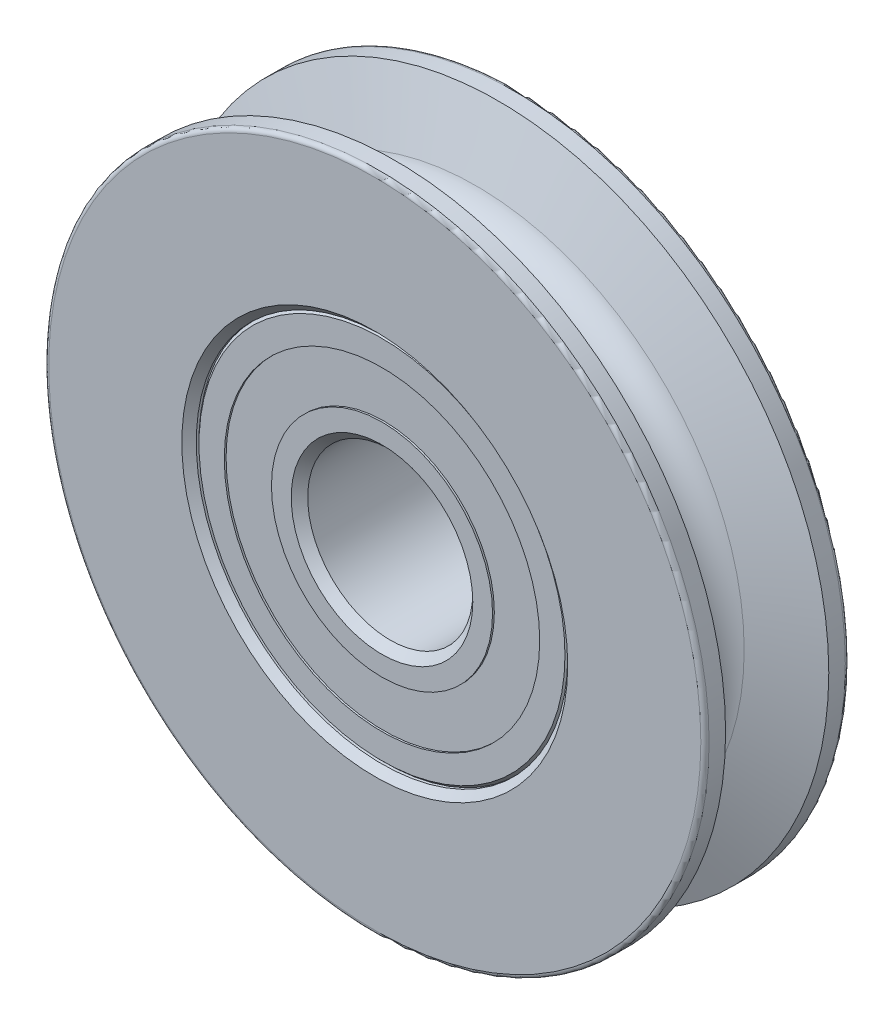
SolidWorks part; units mm, degrees
ref_plane "Front Plane" through (0, 0, 0) normal (0, 0, 1) x (1, 0, 0)
ref_plane "Top Plane" through (0, 0, 0) normal (0, 1, 0) x (1, 0, 0)
ref_plane "Right Plane" through (0, 0, 0) normal (1, 0, 0) x (0, 0, -1)
sketch "Sketch1" plane through (0, 0, 0) normal (1, 0, 0) x (0, 0, -1)
  line L0 (-5.0006, 0) -> (5.0006, 0) construction
  line L1 (-4.3656, 6.35) -> (4.6831, 6.35)
  line L2 (5.0006, 6.6675) -> (5.0006, 14.0758)
  line L3 (4.789, 14.2875) -> (-4.789, 14.2875)
  line L4 (-5.0006, 14.0758) -> (-5.0006, 6.985)
  line L5 (-5.5563, 25.4) -> (-5.5562, 14.8431)
  line L6 (-5.5563, 25.4) -> (-3.9688, 25.4)
  line L7 (0, 0) -> (0, 6.35) construction
  line L8 (-2.2391, 20.6209) -> (-3.9688, 25.4)
  line L9 (5.5563, 25.4) -> (5.5563, 14.8431)
  line L10 (5.5563, 25.4) -> (3.9688, 25.4)
  line L11 (2.2391, 20.6209) -> (3.9688, 25.4)
  line L12 (-5.0006, 6.985) -> (-4.3656, 6.35)
  line L13 (-5.0006, 6.985) -> (-5.0006, 6.35) construction
  line L14 (-5.0006, 6.35) -> (-4.3656, 6.35) construction
  line L15 (-5.0006, 7.62) -> (-4.3656, 6.985)
  line L16 (-4.3656, 6.985) -> (0, 6.985)
  line L17 (-2.2679, 10.3187) -> (2.2679, 10.3187) construction
  line L18 (4.6831, 6.35) -> (5.0006, 6.6675)
  line L19 (4.6831, 6.35) -> (5.0006, 6.35) construction
  line L20 (5.0006, 6.35) -> (5.0006, 6.6675) construction
  line L21 (-2.2679, 10.3187) -> (-5.0006, 10.3187) construction
  line L22 (-5.0006, 12.133) -> (-1.3607, 12.133)
  line L23 (-5.0006, 8.5045) -> (-1.3607, 8.5045)
  line L24 (1.3607, 12.133) -> (5.0006, 12.133)
  line L25 (1.3607, 8.5045) -> (5.0006, 8.5045)
  line L26 (-4.6831, 6.6675) -> (5.0006, 6.6675) construction
  line L27 (0, 6.985) -> (0, 8.0509)
  line L28 (0, 14.2875) -> (0, 19.05) construction
  line L29 (0, 6.985) -> (0, 8.0509) construction
  line L30 (0, 14.2875) -> (0, 6.35) construction
  line L31 (-4.789, 14.2875) -> (-5.0006, 14.0758)
  line L32 (5.0006, 14.0758) -> (4.789, 14.2875)
  line L33 (-5.0006, 14.0758) -> (-5.0006, 14.2875) construction
  line L34 (-5.0006, 14.2875) -> (-4.789, 14.2875) construction
  line L35 (4.789, 14.2875) -> (5.0006, 14.2875) construction
  line L36 (5.0006, 14.2875) -> (5.0006, 14.0758) construction
  line L37 (-5.5562, 14.8431) -> (-5.5562, 14.2875) construction
  line L38 (5.5563, 14.8431) -> (5.5562, 14.2875) construction
  line L39 (-5.5562, 14.8431) -> (-5.0006, 14.2875)
  line L40 (-5.0006, 14.2875) -> (-5.5562, 14.2875) construction
  line L41 (5.0006, 14.2875) -> (5.5562, 14.2875) construction
  line L42 (5.0006, 14.2875) -> (5.5563, 14.8431)
  arc A0 (-2.2391, 20.6209) -> (2.2391, 20.6209) centre (0, 21.4313) ccw
  circle A1 centre (0, 10.3187) radius 2.2679
  point P4 (0, 0)
  point P7 (5.0006, 14.2875)
  point P9 (-5.0006, 14.2875)
  point P43 (0, 10.3187)
  dimension "For Rope Diameter" = 4.7625
  dimension "D2" = 4.5357
  dimension "Pulley Diameter" = 38.1
  dimension "Overall Width" = 10.0012
  dimension "For Shaft Diameter" = 12.7
  dimension "Bearing OD" = 28.575
  dimension "Pulley Width (F)" = 7.9375
  dimension "Width" = 11.1125
  dimension "OD" = 50.8
  dimension "D1" = 3.6286
  dimension "D3" = 0.635
  dimension "D4" = 0.2117
  dimension "D6" = 0.2117
  dimension "D5" = 20.6375
sketch "Sketch2" plane through (0, 0, 0) normal (1, 0, 0) x (0, 0, -1)
  line L0 (-5.0006, 7.62) -> (-5.0006, 6.985)
  line L5 (-5.0006, 6.985) -> (-4.3656, 6.35)
  line L6 (-4.3656, 6.35) -> (4.6831, 6.35)
  line L7 (4.6831, 6.35) -> (5.0006, 6.6675)
  line L8 (5.0006, 6.6675) -> (5.0006, 8.5045)
  line L9 (5.0006, 8.5045) -> (1.3607, 8.5045)
  line L10 (-5.0006, 7.62) -> (-4.3656, 6.985)
  line L11 (-4.3656, 6.985) -> (0, 6.985)
  line L12 (0, 6.985) -> (0, 8.0509)
  circle A0 centre (0, 10.3187) radius 2.2679 construction
  arc A1 (0, 8.0509) -> (1.3607, 8.5045) centre (0, 10.3187) ccw
revolve "Bushing Revolve1" add sketch "Sketch2" angle 360 about L0
sketch "Sketch3" plane through (0, 0, 0) normal (1, 0, 0) x (0, 0, -1)
  line L4 (-5.0006, 8.5045) -> (-5.0006, 7.62)
  line L5 (-5.0006, 7.62) -> (-4.3656, 6.985)
  line L6 (-4.3656, 6.985) -> (0, 6.985)
  line L7 (0, 6.985) -> (0, 8.0509)
  line L20 (-5.0006, 8.5045) -> (-1.3607, 8.5045)
  circle A2 centre (0, 10.3187) radius 2.2679 construction
  arc A3 (-1.3607, 8.5045) -> (0, 8.0509) centre (0, 10.3187) ccw
revolve "Bushing Revolve2" add sketch "Sketch3" angle 360 about L0
sketch "Sketch4" plane through (0, 0, 0) normal (1, 0, 0) x (0, 0, -1)
  line L2 (1.3607, 12.133) -> (5.0006, 12.133) construction
  line L3 (-5.0006, 12.133) -> (-1.3607, 12.133) construction
  line L7 (1.3607, 12.133) -> (5.0006, 12.133)
  line L8 (-5.0006, 12.133) -> (-1.3607, 12.133)
  line L14 (5.0006, 6.6675) -> (5.0006, 14.0758) construction
  line L15 (5.0006, 14.0758) -> (4.789, 14.2875) construction
  line L16 (4.789, 14.2875) -> (-4.789, 14.2875) construction
  line L17 (-4.789, 14.2875) -> (-5.0006, 14.0758) construction
  line L18 (-5.0006, 14.0758) -> (-5.0006, 6.985) construction
  line L19 (5.0006, 12.133) -> (5.0006, 14.0758)
  line L20 (5.0006, 14.0758) -> (4.789, 14.2875)
  line L21 (4.789, 14.2875) -> (-4.789, 14.2875)
  line L22 (-4.789, 14.2875) -> (-5.0006, 14.0758)
  line L23 (-5.0006, 14.0758) -> (-5.0006, 12.133)
  circle A0 centre (0, 10.3187) radius 2.2679 construction
  arc A1 (1.3607, 12.133) -> (-1.3607, 12.133) centre (0, 10.3187) ccw
revolve "Bushing Revolve3" add sketch "Sketch4" angle 360 about L0
sketch "Sketch5" plane through (0, 0, 0) normal (1, 0, 0) x (0, 0, -1)
  line L6 (-4.8617, 12.133) -> (-4.8617, 8.5045)
  line L7 (4.8617, 8.5045) -> (4.8617, 12.133)
  line L8 (1.3607, 8.5045) -> (4.8617, 8.5045)
  line L9 (1.3607, 12.133) -> (4.8617, 12.133)
  line L10 (-4.8617, 8.5045) -> (-1.3607, 8.5045)
  line L11 (-4.8617, 12.133) -> (-1.3607, 12.133)
  line L12 (-1.3607, 12.133) -> (-5.0006, 12.133) construction
  circle A0 centre (0, 10.3187) radius 2.2679 construction
  arc A1 (-1.3607, 12.133) -> (-1.3607, 8.5045) centre (0, 10.3187) ccw
  arc A2 (1.3607, 8.5045) -> (1.3607, 12.133) centre (0, 10.3187) ccw
  dimension "D1" = 9.7234
revolve "Shielding Revolve" add sketch "Sketch5" angle 360 about L0
sketch "Sketch6" plane through (0, 0, 0) normal (1, 0, 0) x (0, 0, -1)
  line L0 (-5.5563, 25.4) -> (-3.9688, 25.4) construction
  line L1 (-2.2391, 20.6209) -> (-3.9688, 25.4) construction
  line L2 (2.2391, 20.6209) -> (3.9688, 25.4) construction
  line L3 (5.5563, 25.4) -> (3.9688, 25.4) construction
  line L7 (-5.2388, 25.4) -> (-3.9688, 25.4)
  line L8 (-2.2391, 20.6209) -> (-3.9688, 25.4)
  line L9 (2.2391, 20.6209) -> (3.9688, 25.4)
  line L10 (5.2388, 25.4) -> (3.9688, 25.4)
  line L11 (5.5563, 25.0825) -> (5.5563, 14.8431)
  line L13 (-5.5563, 25.0825) -> (-5.5562, 14.8431)
  line L14 (-5.5562, 14.8431) -> (-5.0006, 14.2875)
  line L15 (-5.0006, 14.2875) -> (5.0006, 14.2875)
  line L16 (5.0006, 14.2875) -> (5.5563, 14.8431)
  arc A0 (-2.2391, 20.6209) -> (2.2391, 20.6209) centre (0, 21.4313) ccw construction
  arc A1 (-2.2391, 20.6209) -> (2.2391, 20.6209) centre (0, 21.4313) ccw
  arc A2 (5.2388, 25.4) -> (5.5563, 25.0825) centre (5.2388, 25.0825) cw
  arc A3 (-5.2388, 25.4) -> (-5.5563, 25.0825) centre (-5.2388, 25.0825) ccw
  dimension "D1" = 0.3175
revolve "Sheave Revolve" add sketch "Sketch6" angle 360 about L0
sketch "Sketch7" plane through (0, 0, 0) normal (1, 0, 0) x (0, 0, -1)
  line L0 (-2.2679, 10.3187) -> (2.2679, 10.3187) construction
  line L1 (-2.2679, 10.3187) -> (2.2679, 10.3187)
  circle A0 centre (0, 10.3187) radius 2.2679 construction
  arc A1 (2.2679, 10.3187) -> (-2.2679, 10.3187) centre (0, 10.3187) ccw
revolve "Bearing Ball Revolve" add sketch "Sketch7" angle 360 about L1
pattern_circular "Bearing Ball CirPattern" count 11 over 360 about axis through (0, 0, 5.0006) along (0, 0, -1) reverse direction yes of bodies 114
sketch "Sketch8" plane through (0, 0, 0) normal (1, 0, 0) x (0, 0, -1)
  circle A0 centre (0, -21.4313) radius 2.3812 construction
  arc A1 (2.2391, -20.6209) -> (-2.2391, -20.6209) centre (0, -21.4313) ccw construction
equation "\"Overall Width@Sketch1\"=\"Width@Sketch1\" * .9"
equation "\"D1@Sketch1\"=\"D2@Sketch1\"*.8"
equation "\"D6@Sketch1\"=\"D4@Sketch1\""
equation "\"D4@Sketch1\"=\"D3@Sketch1\"/3"
equation "\"D2@Sketch1\"=( \"Bearing OD@Sketch1\" - \"For Shaft Diameter@Sketch1\" )  / 3.5"
equation "\"D1@Bearing Ball CirPattern\"=(180 / 1+ \"D5@Sketch1\")/16"
equation "\"D3@Sketch1\"=\"For Shaft Diameter@Sketch1\"*.05"
equation "\"D1@Sketch5\"=\"Width@Sketch1\" * .875"
